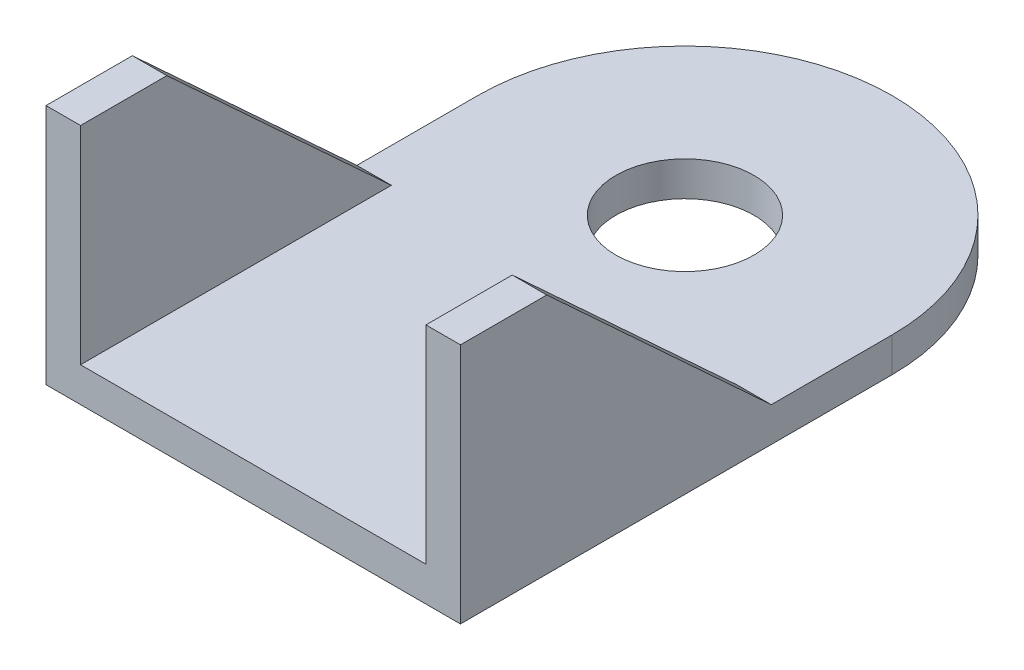
SolidWorks part; units mm, degrees
material "AISI 304"
ref_plane "前视基准面" through (0, 0, 0) normal (0, 0, 1) x (1, 0, 0)
ref_plane "上视基准面" through (0, 0, 0) normal (0, 1, 0) x (1, 0, 0)
ref_plane "右视基准面" through (0, 0, 0) normal (1, 0, 0) x (0, 0, -1)
sketch "草图1" plane through (0, 0, 0) normal (0, 1, 0) x (1, 0, 0)
  line L0 (-12, 0) -> (-12, -25)
  line L1 (-12, -25) -> (12, -25)
  line L2 (12, -25) -> (12, 0)
  circle A0 centre (0, 0) radius 4
  circle A1 centre (0, 0) radius 12
  dimension "D1" = 8
  dimension "D2" = 24
  dimension "D3" = 25
extrude "凸台-拉伸1" add sketch "草图1" along normal blind 2 contours A1 A0 | A1 L0 L1 L2 region at (0, 0, 16.9821) region at (0, 0, -11.6606)
sketch "草图3" plane through (12, 0, 0) normal (1, 0, 0) x (0, 0, -1)
  line L0 (-25, 2) -> (-25, 14)
  line L1 (-25, 14) -> (-20, 14)
  line L2 (-20, 14) -> (-7, 2)
  line L4 (-25, 2) -> (0, 2) construction
  line L5 (-7, 2) -> (-25, 2)
  point P3 (0, 0)
  dimension "D1" = 5
  dimension "D2" = 18
  dimension "D4" = 12
extrude "凸台-拉伸2" add sketch "草图3" against normal blind 2
mirror "镜向1" about plane through (0, 0, 0) normal (1, 0, 0) of "凸台-拉伸2"
ref_plane "基准面1" through (0, 0, 0) normal (0, 0, 1) x (1, 0, 0)
sketch "草图4" [suppressed] plane through (0, 0, 0) normal (0, 0, 1) x (1, 0, 0)
  circle A0 centre (0, 0) radius 41.9162
sketch "草图7" plane through (0, 0, 0) normal (0, -1, 0) x (1, 0, 0)
  circle A0 centre (0, 0) radius 9
split line "分割线1"
sketch "草图8" plane through (0, 0, 0) normal (0, -1, 0) x (1, 0, 0)
  circle A0 centre (0, 0) radius 12
split line "分割线2"
